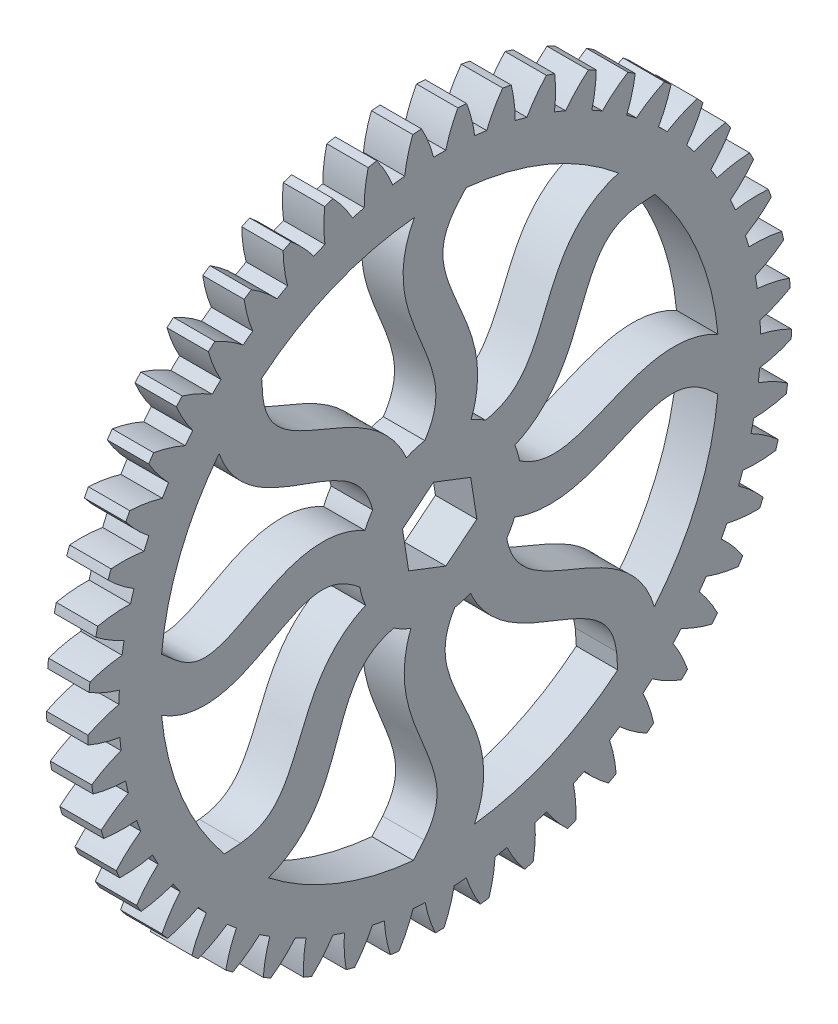
SolidWorks part; units mm, degrees
material "Plain Carbon Steel"
ref_plane "Plane1" through (0, 0, 0) normal (0, 0, 1) x (1, 0, 0)
ref_plane "Plane2" through (0, 0, 0) normal (0, 1, 0) x (1, 0, 0)
ref_plane "Plane3" through (0, 0, 0) normal (1, 0, 0) x (0, 0, -1)
sketch "HoldingSke" plane through (0, 0, 0) normal (0, 1, 0) x (1, 0, 0)
  line L0 (0, 0) -> (0.6561, -0.7547)
  line L1 (-15, 0) -> (100, 0) construction
  line L2 (0, 0) -> (-2.1039, 2.3779)
  line L3 (0, 0) -> (-11.863, 4.5341)
  line L4 (0, 0) -> (5.6657, 6.5177)
  line L5 (0, 0) -> (-46.8476, -17.4728)
  line L6 (0, 0) -> (-2.4869, -1.6779)
  line L7 (-2.1039, 2.3779) -> (8.6586, 51.2059)
  line L8 (-76.2, 54.61) -> (-75.7, 54.61)
  line L9 (-71.009, 38.7566) -> (-53.1078, 45.2721)
  line L10 (-76.2, 71.12) -> (104.1128, 71.12)
  line L11 (0, 0) -> (-3, 0)
  line L12 (-76.2, 101.6) -> (-76.162, 101.6)
  line L13 (24.9733, 27.94) -> (52.9518, 28.4284)
  line L14 (24.9733, 27.94) -> (24.9743, 27.94)
  line L15 (24.9733, 27.94) -> (100.4006, 29.5858)
  line L16 (-63.627, -1) -> (-12.827, -1)
  circle A0 centre (0, 0) radius 1.5
  circle A1 centre (0, 0) radius 23.249
  circle A2 centre (0, 0) radius 37.5
  circle A3 centre (0, 0) radius 1.5
  dimension "MHD" = 46.498
  dimension "Hub_dia" = 75
  dimension "Bore" = 3
  dimension "MBD" = 3
  dimension "Num_teeth" = 49
  dimension "Pitch_radius" = 180.3128
  dimension "Pitch" = 1
  dimension "Width" = 3
  dimension "Overall_len" = 50
  dimension "Show_teeth" = 49
  dimension "Thickness" = 3
  dimension "OAL" = 50.0001
  dimension "T_dim" = 0.5
  dimension "Ap" = 20
  dimension "H" = 19.05
  dimension "Backlash" = 0.038
  dimension "Addendum_fac" = 1
  dimension "Dedendum_fac" = 1.25
  dimension "Clearance_fac" = 0.25
  dimension "Dedendum_add" = 0.001
  dimension "Module" = 1
sketch "BasProSke" plane through (0, 0, 0) normal (0, 1, 0) x (1, 0, 0)
  line L0 (-10, 0) -> (60, 0) construction
  line L1 (0, 0) -> (0, 25.5)
  line L2 (0, 0) -> (3, 0)
  line L3 (3, 0) -> (3, 25.5)
  line L4 (3, 25.5) -> (0, 25.5)
  dimension "Diameter" = 51
  dimension "Thickness" = 3
revolve "Base-Revolve" add sketch "BasProSke" angle 360 about L0
sketch "TooCutSke" plane through (0, 0, 0) normal (1, 0, 0) x (0, 0, -1)
  line L1 (0, 0) -> (0, 107) construction
  line L2 (0, 0) -> (-0.8518, 24.4852) construction
  line L3 (0, 0) -> (-3.1381, 48.8783) construction
  line L4 (-0.8518, 24.4852) -> (-1.569, 24.4391) construction
  arc A0 (0.4386, 23.2449) -> (-0.4386, 23.2449) centre (0, 0) ccw
  arc A1 (1.3315, 25.4906) -> (-1.3315, 25.4906) centre (0, 0) ccw
  circle A2 centre (0, 0) radius 24.5 construction
  circle A3 centre (0, 0) radius 23.0225 construction
  arc A4 (-0.4386, 23.2449) -> (-1.3315, 25.4906) centre (-9.9221, 20.7746) ccw
  arc A5 (1.3315, 25.4906) -> (0.4386, 23.2449) centre (9.9221, 20.7746) ccw
  dimension "Root_dia" = 46.498
  dimension "Overcut_dia" = 51.0508
  dimension "Pitch_dia" = 49
  dimension "Base_dia" = 46.0449
  dimension "Flank_rad" = 9.8
  dimension "Half_ang" = 3.673
  dimension "Half_CT" = 0.7188
extrude "ToothCut" cut sketch "TooCutSke" along normal through all
fillet "Breaks" [suppressed] radius 0.02 tangent propagation no
fillet "RootFillets" [suppressed] radius 0.251
pattern_circular "TeethCuts" count 49 every 7.347 about axis through (-10, 0, 0) along (1, 0, 0) of "ToothCut", "RootFillets", "Breaks"
sketch "HubNeaOneSke" plane through (0, 0, 0) normal (-1, 0, 0) x (0, 0, 1)
  circle A0 centre (0, 0) radius 23.249
  dimension "Diameter" = 46.498
extrude "HubNearOne" [suppressed] add sketch "HubNeaOneSke" along normal blind 47.0001
sketch "HubNeaBotSke" plane through (0, 0, 0) normal (-1, 0, 0) x (0, 0, 1)
  circle A0 centre (0, 0) radius 23.249
  dimension "Diameter" = 46.498
extrude "HubNearBoth" [suppressed] add sketch "HubNeaBotSke" along normal blind 23.5
ref_plane "FarPln" through (3, 0, 0) normal (1, 0, 0) x (0, 0, -1)
sketch "HubFarSke" plane through (3, 0, 0) normal (1, 0, 0) x (0, 0, -1)
  circle A0 centre (0, 0) radius 23.249
  dimension "Diameter" = 46.498
extrude "HubFar" [suppressed] add sketch "HubFarSke" along normal blind 23.5
sketch "BorSke" plane through (0, 0, 0) normal (1, 0, 0) x (0, 0, -1)
  line L1 (-2.8868, 0) -> (-1.4434, -2.5) construction
  line L2 (-1.4434, -2.5) -> (1.4434, -2.5) construction
  line L3 (1.4434, -2.5) -> (2.8868, 0) construction
  line L4 (2.8868, 0) -> (1.4434, 2.5) construction
  line L5 (1.4434, 2.5) -> (-1.4434, 2.5) construction
  line L6 (-1.4434, 2.5) -> (-2.8868, 0) construction
  circle A0 centre (0, 0) radius 1.5
  circle A1 centre (0, 0) radius 2.5 construction
  dimension "D1" = 5
  dimension "Diameter" = 3
extrude "Bore" cut sketch "BorSke" along normal mid plane 100.0001
sketch "KeySke" plane through (0, 0, 0) normal (1, 0, 0) x (0, 0, -1)
  line L0 (-0.6, 0) -> (-0.6, 2)
  line L1 (-0.6, 2) -> (0.6, 2)
  line L2 (0.6, 2) -> (0.6, 0)
  line L3 (0, 0) -> (0, 34) construction
  line L4 (-0.6, 0) -> (0.6, 0)
  dimension "Offset" = 2
  dimension "Width" = 1.2
extrude "Keyway" [suppressed] cut sketch "KeySke" along normal mid plane 100.0001
pattern_circular "Keyway2" [suppressed] count 2 every 90 about axis through (-10, 0, 0) along (1, 0, 0)
sketch "Sketch1" plane through (0, 0, 0) normal (-1, 0, 0) x (0, 0, 1)
  line L0 (2.8868, 0) -> (5.8868, 0) construction
  line L1 (20.249, 0) -> (5.8868, 0) construction
  line L2 (20.249, 0) -> (23.249, 0) construction
  line L3 (19.2628, 1.1302) -> (20.1585, 1.9118)
  line L4 (5.7215, -1.1285) -> (4.8183, -3.3819)
  line L5 (14.42, -12.8217) -> (15.6061, -12.9024)
  line L6 (3.2477, -4.8436) -> (1.0157, -5.7985)
  line L7 (1.1302, -19.2628) -> (1.9118, -20.1585)
  line L8 (-1.1285, -5.7215) -> (-3.3819, -4.8183)
  line L9 (-12.8217, -14.42) -> (-12.9024, -15.6061)
  line L10 (-4.8436, -3.2477) -> (-5.7985, -1.0157)
  line L11 (-19.2628, -1.1302) -> (-20.1585, -1.9118)
  line L12 (-5.7215, 1.1285) -> (-4.8183, 3.3819)
  line L13 (-14.42, 12.8217) -> (-15.6061, 12.9024)
  line L14 (-3.2477, 4.8436) -> (-1.0157, 5.7985)
  line L15 (-1.1302, 19.2628) -> (-1.9118, 20.1585)
  line L16 (1.1285, 5.7215) -> (3.3819, 4.8183)
  line L17 (11.1265, 15.7649) -> (11.0739, 16.9526)
  line L18 (4.4496, 3.7696) -> (5.6483, 1.6585)
  line L19 (2.685, -5.1768) -> (0.3601, -5.8757)
  line L20 (-5.3883, 18.5283) -> (-6.3496, 19.2277)
  line L21 (12.8938, -14.3556) -> (14.0634, -14.5686)
  line L22 (-2.3733, -5.3269) -> (-4.3693, -3.945)
  line L23 (-5.6445, -1.4657) -> (-5.8085, 0.9564)
  line L24 (-4.6652, 3.4992) -> (-2.8738, 5.1376)
  line L25 (-0.173, 5.8291) -> (2.2249, 5.4501)
  line L26 (-17.8456, 7.3395) -> (-18.9917, 7.024)
  line L27 (-16.8648, -9.3761) -> (-17.3327, -10.469)
  line L28 (-3.1845, -19.0313) -> (-2.6218, -20.0786)
  line L29 (12.8217, 14.42) -> (12.9024, 15.6061)
  line L30 (4.8436, 3.2477) -> (5.7985, 1.0157)
  circle A0 centre (0, 0) radius 5.8868
  circle A1 centre (0, 0) radius 23.249 construction
  circle A2 centre (0, 0) radius 20.249
  spline S0 degree 3 poles (20.249, 0) (14.621, -4.9109) (10.9351, 5.4308) (4.7333, 0) knots 0 0 0 0 1 1 1 1 construction
  spline S1 degree 1 poles (19.2628, 1.1302) (3.7451, 1.1285) knots 0 0 1 1 construction
  spline S2 degree 3 poles (19.2628, 1.1302) (19.1293, 1.0138) (18.8376, 0.7808) (18.3339, 0.4567) (17.7715, 0.2166) (17.178, 0.1175) (16.3645, 0.1613) (15.163, 0.5668) (13.4561, 1.4991) (11.5183, 2.5306) (9.5885, 3.1305) (7.8275, 3.1388) (6.4544, 2.8313) (5.3119, 2.2876) (4.4177, 1.687) (3.9611, 1.3177) (3.7451, 1.1285) knots 0 0 0 0 0.03125 0.0625 0.125 0.1875 0.25 0.375 0.5 0.625 0.75 0.8125 0.875 0.9375 0.96875 1 1 1 1 only from (19.2628, 1.1302) to (5.4145, 2.3102)
  spline S3 degree 1 poles (21.2352, -1.1302) (5.7215, -1.1285) knots 0 0 1 1 construction
  spline S4 degree 3 poles (21.2352, -1.1302) (21.0332, -1.3065) (20.6054, -1.6485) (19.7572, -2.1994) (18.2169, -2.8765) (16.0114, -2.9359) (13.8328, -2.1307) (11.9654, -1.1014) (10.276, -0.2178) (9.0516, 0.1315) (8.1569, 0.1303) (7.4619, -0.0214) (6.7968, -0.3317) (6.2097, -0.7234) (5.8756, -0.9935) (5.7215, -1.1285) knots 0 0 0 0 0.03125 0.0625 0.125 0.25 0.375 0.5 0.625 0.75 0.8125 0.875 0.9375 0.96875 1 1 1 1 only from (20.1564, -1.9342) to (5.7215, -1.1285)
  spline S5 degree 3 poles (14.42, -12.8217) (14.2582, -12.8026) (13.9229, -12.7485) (13.3679, -12.6041) (12.7932, -12.3588) (12.2429, -11.9773) (11.6038, -11.331) (10.9146, -10.2125) (10.1792, -8.4567) (9.3709, -6.4927) (8.2199, -4.4964) (6.6749, -3.0349) (5.2192, -2.3229) (4.4625, -2.0781) (4.0808, -1.9789) (3.8352, -1.9214) (3.651, -1.8843) (3.5434, -1.8646) knots 0 0 0 0 0.03125 0.0625 0.125 0.1875 0.25 0.375 0.5 0.625 0.75 0.875 0.9375 0.96875 0.97755 0.98653 1 1 1 1
  spline S6 degree 3 poles (13.7854, -16.3368) (13.5386, -16.2959) (13.1873, -16.2223) (12.7413, -16.0987) (12.4785, -16.0136) (11.9085, -15.8059) (10.665, -15.1995) (9.1813, -13.763) (8.1187, -11.7584) (7.4026, -9.7726) (6.7462, -7.9552) (6.0949, -6.7348) (5.4563, -5.9802) (4.8946, -5.5111) (4.3092, -5.1875) (3.7476, -4.9747) (3.4115, -4.8817) (3.2477, -4.8436) knots 0 0 0 0 0.03125 0.044052 0.059677 0.06749 0.125 0.25 0.375 0.5 0.625 0.75 0.8125 0.875 0.9375 0.96875 1 1 1 1
  spline S7 degree 3 poles (1.1302, -19.2628) (1.0293, -19.1349) (0.8304, -18.8595) (0.5401, -18.365) (0.3072, -17.7851) (0.1878, -17.1263) (0.1929, -16.2173) (0.4965, -14.9391) (1.2179, -13.1776) (2.0352, -11.2173) (2.6329, -8.9918) (2.5738, -6.8659) (2.048, -5.3331) (1.686, -4.6249) (1.4863, -4.2849) (1.3532, -4.0706) (1.2492, -3.9141) (1.1871, -3.824) knots 0 0 0 0 0.03125 0.0625 0.125 0.1875 0.25 0.375 0.5 0.625 0.75 0.875 0.9375 0.96875 0.97755 0.98653 1 1 1 1
  spline S8 degree 3 poles (-1.8041, -21.2996) (-1.9497, -21.0961) (-2.1461, -20.7958) (-2.374, -20.3929) (-2.4997, -20.147) (-2.7559, -19.597) (-3.2064, -18.289) (-3.2397, -16.224) (-2.5736, -14.0552) (-1.6758, -12.1447) (-0.8549, -10.3954) (-0.4525, -9.0719) (-0.3705, -8.0869) (-0.4359, -7.3579) (-0.6211, -6.7152) (-0.8677, -6.1676) (-1.0396, -5.8641) (-1.1285, -5.7215) knots 0 0 0 0 0.03125 0.044052 0.059677 0.06749 0.125 0.25 0.375 0.5 0.625 0.75 0.8125 0.875 0.9375 0.96875 1 1 1 1
  spline S9 degree 3 poles (-12.8217, -14.42) (-12.8, -14.2585) (-12.7405, -13.9241) (-12.5872, -13.3716) (-12.3325, -12.8009) (-11.9422, -12.2568) (-11.2856, -11.6282) (-10.1561, -10.9572) (-8.3887, -10.2503) (-6.4119, -9.4739) (-4.3973, -8.3554) (-2.911, -6.8341) (-2.1755, -5.3901) (-1.9185, -4.6375) (-1.8132, -4.2575) (-1.7517, -4.0128) (-1.7116, -3.8293) (-1.6902, -3.722) knots 0 0 0 0 0.03125 0.0625 0.125 0.1875 0.25 0.375 0.5 0.625 0.75 0.875 0.9375 0.96875 0.97755 0.98653 1 1 1 1
  spline S10 degree 3 poles (-15.8291, -14.3136) (-15.7999, -14.0651) (-15.7429, -13.7108) (-15.6403, -13.2595) (-15.5677, -12.993) (-15.387, -12.4139) (-14.8397, -11.1432) (-13.4744, -9.5937) (-11.5219, -8.4381) (-9.572, -7.6296) (-7.7874, -6.8885) (-6.599, -6.1806) (-5.8752, -5.5073) (-5.433, -4.9241) (-5.1373, -4.3242) (-4.9511, -3.7532) (-4.8739, -3.4131) (-4.8436, -3.2477) knots 0 0 0 0 0.03125 0.044052 0.059677 0.06749 0.125 0.25 0.375 0.5 0.625 0.75 0.8125 0.875 0.9375 0.96875 1 1 1 1
  spline S11 degree 3 poles (-19.2628, -1.1302) (-19.1332, -1.0314) (-18.8548, -0.8369) (-18.3556, -0.5547) (-17.772, -0.3312) (-17.1113, -0.2225) (-16.2025, -0.2423) (-14.9294, -0.5664) (-13.1798, -1.3163) (-11.233, -2.1652) (-9.0175, -2.7988) (-6.8908, -2.7741) (-5.3497, -2.2731) (-4.6358, -1.9227) (-4.2926, -1.7284) (-4.0761, -1.5988) (-3.918, -1.4974) (-3.827, -1.4367) knots 0 0 0 0 0.03125 0.0625 0.125 0.1875 0.25 0.375 0.5 0.625 0.75 0.875 0.9375 0.96875 0.97755 0.98653 1 1 1 1
  spline S12 degree 3 poles (-21.3142, 1.0716) (-21.1177, 1.2266) (-20.8269, 1.4369) (-20.4352, 1.6835) (-20.1955, 1.8206) (-19.6582, 2.1023) (-18.3727, 2.6138) (-16.3116, 2.7441) (-14.1139, 2.1806) (-12.1634, 1.3735) (-10.3774, 0.6356) (-9.0365, 0.2959) (-8.0487, 0.2602) (-7.3236, 0.3598) (-6.6903, 0.575) (-6.1549, 0.847) (-5.8598, 1.033) (-5.7215, 1.1285) knots 0 0 0 0 0.03125 0.044052 0.059677 0.06749 0.125 0.25 0.375 0.5 0.625 0.75 0.8125 0.875 0.9375 0.96875 1 1 1 1
  spline S13 degree 3 poles (-14.42, 12.8217) (-14.2585, 12.8) (-13.9241, 12.7405) (-13.3716, 12.5872) (-12.8009, 12.3325) (-12.2568, 11.9422) (-11.6282, 11.2856) (-10.9572, 10.1561) (-10.2503, 8.3887) (-9.4739, 6.4119) (-8.3554, 4.3973) (-6.8341, 2.911) (-5.3901, 2.1755) (-4.6375, 1.9185) (-4.2575, 1.8132) (-4.0128, 1.7517) (-3.8293, 1.7116) (-3.722, 1.6902) knots 0 0 0 0 0.03125 0.0625 0.125 0.1875 0.25 0.375 0.5 0.625 0.75 0.875 0.9375 0.96875 0.97755 0.98653 1 1 1 1
  spline S14 degree 3 poles (-14.3136, 15.8291) (-14.0651, 15.7999) (-13.7108, 15.7429) (-13.2595, 15.6403) (-12.993, 15.5677) (-12.4139, 15.387) (-11.1432, 14.8397) (-9.5937, 13.4744) (-8.4381, 11.5219) (-7.6296, 9.572) (-6.8885, 7.7874) (-6.1806, 6.599) (-5.5073, 5.8752) (-4.9241, 5.433) (-4.3242, 5.1373) (-3.7532, 4.9511) (-3.4131, 4.8739) (-3.2477, 4.8436) knots 0 0 0 0 0.03125 0.044052 0.059677 0.06749 0.125 0.25 0.375 0.5 0.625 0.75 0.8125 0.875 0.9375 0.96875 1 1 1 1
  spline S15 degree 3 poles (-1.1302, 19.2628) (-1.0314, 19.1332) (-0.8369, 18.8548) (-0.5547, 18.3556) (-0.3312, 17.772) (-0.2225, 17.1113) (-0.2423, 16.2025) (-0.5664, 14.9294) (-1.3163, 13.1798) (-2.1652, 11.233) (-2.7988, 9.0175) (-2.7741, 6.8908) (-2.2731, 5.3497) (-1.9227, 4.6358) (-1.7284, 4.2926) (-1.5988, 4.0761) (-1.4974, 3.918) (-1.4367, 3.827) knots 0 0 0 0 0.03125 0.0625 0.125 0.1875 0.25 0.375 0.5 0.625 0.75 0.875 0.9375 0.96875 0.97755 0.98653 1 1 1 1
  spline S16 degree 3 poles (1.0716, 21.3142) (1.2266, 21.1177) (1.4369, 20.8269) (1.6835, 20.4352) (1.8206, 20.1955) (2.1023, 19.6582) (2.6138, 18.3727) (2.7441, 16.3116) (2.1806, 14.1139) (1.3735, 12.1634) (0.6356, 10.3774) (0.2959, 9.0365) (0.2602, 8.0487) (0.3598, 7.3236) (0.575, 6.6903) (0.847, 6.1549) (1.033, 5.8598) (1.1285, 5.7215) knots 0 0 0 0 0.03125 0.044052 0.059677 0.06749 0.125 0.25 0.375 0.5 0.625 0.75 0.8125 0.875 0.9375 0.96875 1 1 1 1
  spline S17 degree 3 poles (12.8217, 14.42) (12.8026, 14.2582) (12.7485, 13.9229) (12.6041, 13.3679) (12.3588, 12.7932) (11.9773, 12.2429) (11.331, 11.6038) (10.2125, 10.9146) (8.4567, 10.1792) (6.4927, 9.3709) (4.4964, 8.2199) (3.0349, 6.6749) (2.3229, 5.2192) (2.0781, 4.4625) (1.9789, 4.0808) (1.9214, 3.8352) (1.8843, 3.651) (1.8646, 3.5434) knots 0 0 0 0 0.03125 0.0625 0.125 0.1875 0.25 0.375 0.5 0.625 0.75 0.875 0.9375 0.96875 0.97755 0.98653 1 1 1 1
  spline S18 degree 3 poles (16.3368, 13.7854) (16.2959, 13.5386) (16.2223, 13.1873) (16.0987, 12.7413) (16.0136, 12.4785) (15.8059, 11.9085) (15.1995, 10.665) (13.763, 9.1813) (11.7584, 8.1187) (9.7726, 7.4026) (7.9552, 6.7462) (6.7348, 6.0949) (5.9802, 5.4563) (5.5111, 4.8946) (5.1875, 4.3092) (4.9747, 3.7476) (4.8817, 3.4115) (4.8436, 3.2477) knots 0 0 0 0 0.03125 0.044052 0.059677 0.06749 0.125 0.25 0.375 0.5 0.625 0.75 0.8125 0.875 0.9375 0.96875 1 1 1 1
  dimension "D1" = 3
  dimension "D2" = 3
  dimension "D3" = 1.5
  dimension "D4" = 1.5
  dimension "D5" = 7
  dimension "D6" = 8
extrude "Cut-Extrude1" cut sketch "Sketch1" against normal blind 10 contours A2 S18 L30 S2 L3 | S5 L5 A2 S4 L4 | S7 L7 A2 S6 L6 | S9 L9 A2 S8 L8 | S11 L11 A2 S10 L10 | S13 L13 A2 S12 L12 | S15 L15 A2 S14 L14 | S17 L29 A2 S16 L16 region at (0, 5.1984, 13.9187) region at (0, -5.8765, 13.2791) region at (0, 13.3918, 5.9464) region at (0, -13.7392, 5.0688) region at (0, 13.728, -5.3138) region at (0, -13.3742, -6.1373) region at (0, 5.9497, -13.4646) region at (0, -5.3139, -13.728)
sketch "Sketch2" plane through (0, 0, 0) normal (-1, 0, 0) x (0, 0, 1)
  line L1 (2.6928, 1.0402) -> (0.4456, 2.8522)
  line L2 (0.4456, 2.8522) -> (-2.2472, 1.812)
  line L3 (-2.2472, 1.812) -> (-2.6928, -1.0402)
  line L4 (-2.6928, -1.0402) -> (-0.4456, -2.8522)
  line L5 (-0.4456, -2.8522) -> (2.2472, -1.812)
  line L6 (2.2472, -1.812) -> (2.6928, 1.0402)
  circle A0 centre (0, 0) radius 2.5 construction
  dimension "D1" = 5
extrude "Cut-Extrude2" cut sketch "Sketch2" against normal blind 10
ref_plane "Plane4" through (1.5, 0, 0) normal (-1, 0, 0) x (0, 0, 1)
equation "' \"Module@HoldingSke\" = 6.35"
equation "' \"Num_teeth@HoldingSke\" = 12"
equation "' \"Ap@HoldingSke\" =  20"
equation "' \"Width@HoldingSke\" = 0.5 * 25.4"
equation "' \"Hub_dia@HoldingSke\"= 1 * 25.4"
equation "' \"Overall_len@HoldingSke\" = 1.0 * 25.4"
equation "' \"Bore@HoldingSke\" = 0.75 * 25.4"
equation "' \"T_dim@HoldingSke\" = 0.1 * 25.4"
equation "' \"Width@KeySke\" = 0.25 * 25.4"
equation "' \"Show_teeth@HoldingSke\" = 13"
equation "' \"Backlash@HoldingSke\" = 0.009 * 25.4"
equation "' \"Addendum_fac@HoldingSke\" = 1.0"
equation "' \"Dedendum_fac@HoldingSke\" = 1.25"
equation "' \"Dedendum_add@HoldingSke\" = 0.00005 * 25.4"
equation "' \"Clearance_fac@HoldingSke\" = 0.25"
equation "\"Pitch@HoldingSke\" = 1 / \"Module@HoldingSke\""
equation "\"Overcut_dia@TooCutSke\" = (\"Num_teeth@HoldingSke\" + 2 * \"Addendum_fac@HoldingSke\") / \"Pitch@HoldingSke\" + 0.002 * 25.4"
equation "\"Pitch_dia@TooCutSke\" = \"Num_teeth@HoldingSke\" / \"Pitch@HoldingSke\""
equation "\"Base_dia@TooCutSke\" = \"Num_teeth@HoldingSke\" / \"Pitch@HoldingSke\" * cos((\"Ap@HoldingSke\"  * 3.14159265 / 180))"
equation "\"Root_dia@TooCutSke\" = (\"Num_teeth@HoldingSke\" + 2) / \"Pitch@HoldingSke\" - 2 * (\"Addendum_fac@HoldingSke\" + \"Dedendum_fac@HoldingSke\") / \"Pitch@HoldingSke\" - \"Dedendum_add@HoldingSke\" * 2"
equation "\"Half_ang@TooCutSke\" = 180 / \"Num_teeth@HoldingSke\""
equation "\"Half_CT@TooCutSke\" = \"Num_teeth@HoldingSke\" / \"Pitch@HoldingSke\" * sin((3.14159265 / 2 / \"Num_teeth@HoldingSke\")) / 2 - 7 * \"Backlash@HoldingSke\" / 4"
equation "\"Flank_rad@TooCutSke\" = \"Num_teeth@HoldingSke\" / \"Pitch@HoldingSke\" / 5"
equation "\"Radius@RootFillets\" = \"Clearance_fac@HoldingSke\" / \"Pitch@HoldingSke\" + \"Dedendum_add@HoldingSke\""
equation "\"Break_rad@Breaks\" = 0.02 / \"Pitch@HoldingSke\""
equation "\"Thickness@HoldingSke\" = \"Width@HoldingSke\""
equation "\"OAL@HoldingSke\" = \"Thickness@HoldingSke\""
equation "\"MHD@HoldingSke\" = (\"Num_teeth@HoldingSke\" + 2) / \"Pitch@HoldingSke\" - 2 * (\"Addendum_fac@HoldingSke\" + \"Dedendum_fac@HoldingSke\")  / \"Pitch@HoldingSke\" - \"Dedendum_add@HoldingSke\" * 2"
equation "\"MBD@HoldingSke\" = (\"Num_teeth@HoldingSke\" + 2) / \"Pitch@HoldingSke\" - 2 * (\"Addendum_fac@HoldingSke\" + \"Dedendum_fac@HoldingSke\")  / \"Pitch@HoldingSke\" - \"Dedendum_add@HoldingSke\" * 2 - 0.002 * 25.4"
equation "\"MHD@HoldingSke\" = ((sgn( \"MHD@HoldingSke\" - \"Hub_dia@HoldingSke\" )-1)*( \"MHD@HoldingSke\" - \"Hub_dia@HoldingSke\" ))/-2+ \"Hub_dia@HoldingSke\""
equation "\"MBD@HoldingSke\" = ((sgn( \"MBD@HoldingSke\" - \"Bore@HoldingSke\" )-1)*( \"MBD@HoldingSke\" - \"Bore@HoldingSke\" ))/-2+ \"Bore@HoldingSke\""
equation "\"OAL@HoldingSke\" = ((sgn( \"OAL@HoldingSke\" - \"Overall_len@HoldingSke\" )+1)*( \"OAL@HoldingSke\" - \"Overall_len@HoldingSke\" ))/2 + \"Overall_len@HoldingSke\" + 0.000002 * 25.4"
equation "\"Num_teeth@TeethCuts\" = int( \"Show_teeth@HoldingSke\" ) + 1"
equation "\"Num_teeth@TeethCuts\" = ((sgn( \"Num_teeth@TeethCuts\" - \"Num_teeth@HoldingSke\" )-1)*( \"Num_teeth@TeethCuts\" - \"Num_teeth@HoldingSke\" ))/-2+ \"Num_teeth@HoldingSke\""
equation "\"Num_teeth@TeethCuts\" = ((sgn( \"Num_teeth@TeethCuts\" - 2.0)+1)*( \"Num_teeth@TeethCuts\" - 2.0))/2 +2.0"
equation "\"Angle@TeethCuts\" = 360.0 / \"Num_teeth@HoldingSke\""
equation "\"Diameter@BasProSke\" = (\"Num_teeth@HoldingSke\" + 2 * \"Addendum_fac@HoldingSke\") / \"Pitch@HoldingSke\""
equation "\"Thickness@BasProSke\"  = \"Thickness@HoldingSke\""
equation "' \"Fillet_rad@BasProSke\" =  \"Thickness@HoldingSke\" * 0.05"
equation "\"MHD@HoldingSke\" = ((sgn( \"MHD@HoldingSke\" - \"Root_dia@TooCutSke\" )-1)*( \"MHD@HoldingSke\" - \"Root_dia@TooCutSke\" ))/-2+ \"Root_dia@TooCutSke\""
equation "\"Diameter@HubNeaOneSke\" = \"MHD@HoldingSke\""
equation "\"Length@HubNearOne\" = \"OAL@HoldingSke\" - \"Thickness@BasProSke\""
equation "\"Diameter@HubNeaBotSke\" = \"MHD@HoldingSke\""
equation "\"Length@HubNearBoth\" = ( \"OAL@HoldingSke\" - \"Thickness@BasProSke\" ) / 2.0"
equation "\"Thickness@FarPln\" = \"Thickness@BasProSke\""
equation "\"Diameter@HubFarSke\" = \"MHD@HoldingSke\""
equation "\"Length@HubFar\" = ( \"OAL@HoldingSke\" - \"Thickness@BasProSke\" ) / 2.0"
equation "\"Diameter@BorSke\" = \"MBD@HoldingSke\""
equation "\"D1@Bore\" = \"OAL@HoldingSke\" * 2.0"
equation "\"D1@Keyway\" = \"OAL@HoldingSke\" * 2.0"
equation "\"Offset@KeySke\" = \"T_dim@HoldingSke\" + \"MBD@HoldingSke\" / 2.0"
